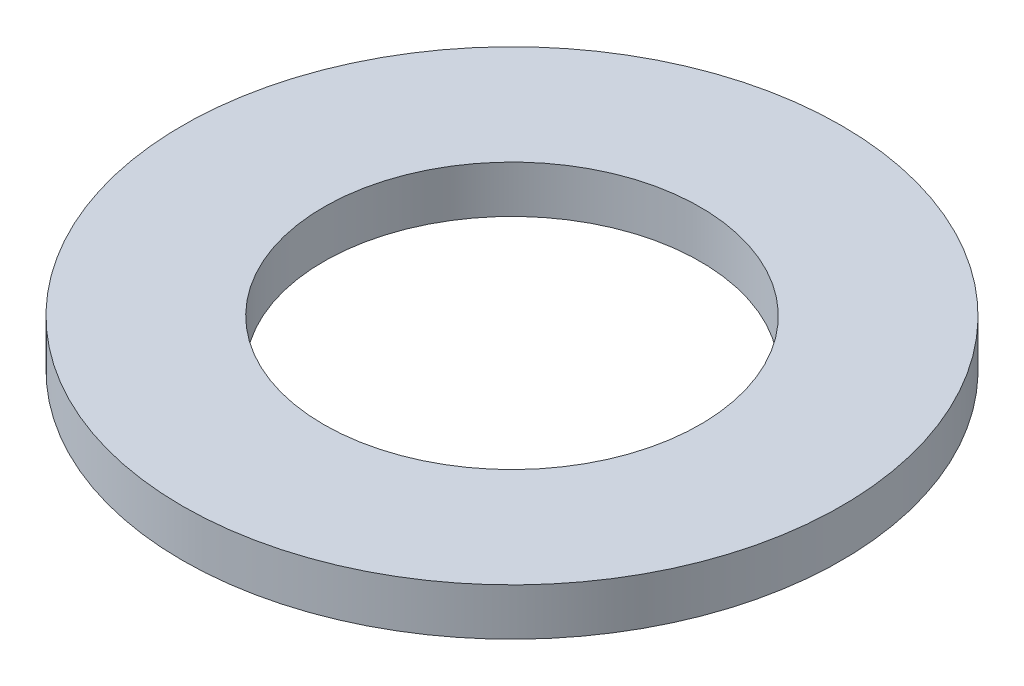
SolidWorks part; units mm, degrees
ref_plane "Front Plane" through (0, 0, 0) normal (0, 0, 1) x (1, 0, 0)
ref_plane "Top Plane" through (0, 0, 0) normal (0, 1, 0) x (1, 0, 0)
ref_plane "Right Plane" through (0, 0, 0) normal (1, 0, 0) x (0, 0, -1)
sketch "Sketch1" plane through (0, 0, 0) normal (0, 1, 0) x (1, 0, 0)
  circle A0 centre (0, 0) radius 70
  dimension "FLANGE_OD" = 140
extrude "Boss-Extrude1" add sketch "Sketch1" along normal blind 10
sketch "Sketch2" plane through (0, 0, 0) normal (0, 1, 0) x (1, 0, 0)
  circle A0 centre (0, 0) radius 40
  dimension "BORE_D" = 80
extrude "Cut-Extrude1" cut sketch "Sketch2" along normal through all
sketch "Sketch3" plane through (0, 10, 0) normal (0, 1, 0) x (1, 0, 0)
  circle A0 centre (0, 0) radius 28.8452 construction
  circle A1 centre (-28.8452, 0) radius 5.0671
  dimension "BOLT_D" = 10.1341
  dimension "BOLT_PCD" = 57.6903
extrude "Cut-Extrude2" cut sketch "Sketch3" against normal blind 6.8467 rebuild error yes
pattern_circular "CirPattern1" count 3 over 360 rebuild error yes
